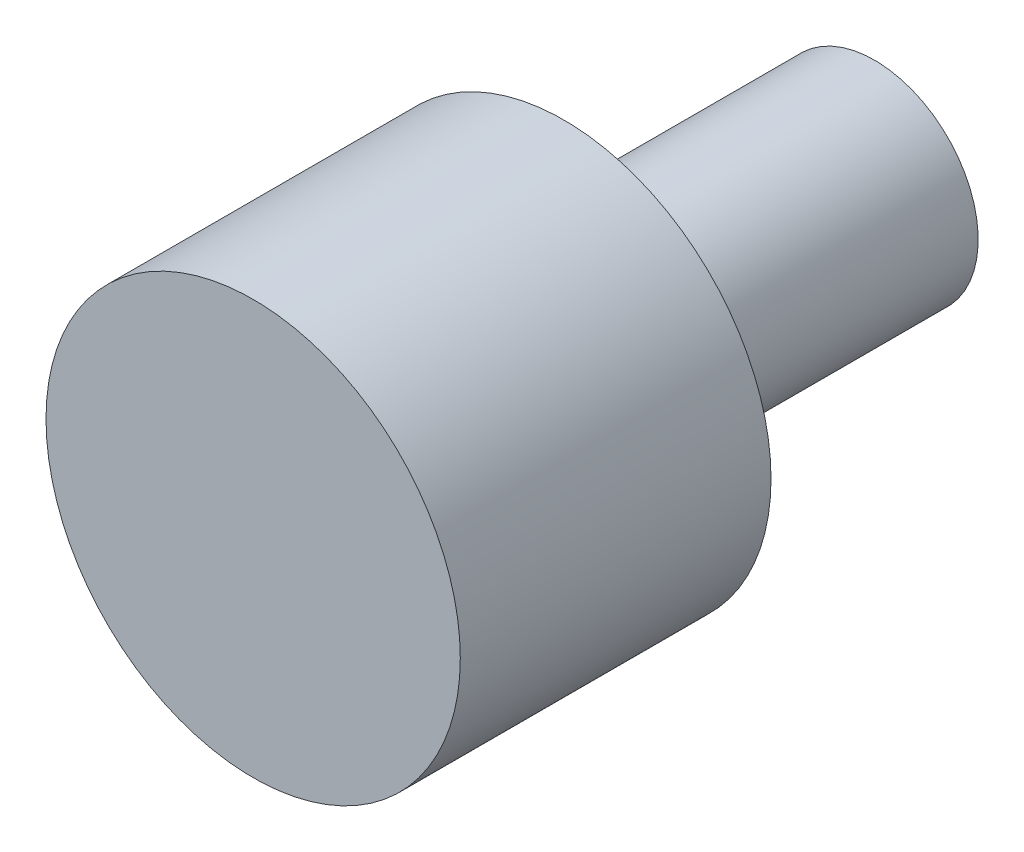
SolidWorks part; units mm, degrees
ref_plane "Front Plane" through (0, 0, 0) normal (0, 0, 1) x (1, 0, 0)
ref_plane "Top Plane" through (0, 0, 0) normal (0, 1, 0) x (1, 0, 0)
ref_plane "Right Plane" through (0, 0, 0) normal (1, 0, 0) x (0, 0, -1)
sketch "Sketch1" plane through (0, 0, 0) normal (0, 0, 1) x (1, 0, 0)
  circle A1 centre (0, 0) radius 20
  dimension "D1" = 40
extrude "Boss-Extrude1" add sketch "Sketch1" along normal blind 30
sketch "Sketch2" plane through (0, 0, 0) normal (0, 0, -1) x (-1, 0, 0)
  circle A0 centre (0, 0) radius 10
  dimension "D1" = 20
extrude "Boss-Extrude2" add sketch "Sketch2" along normal blind 30
